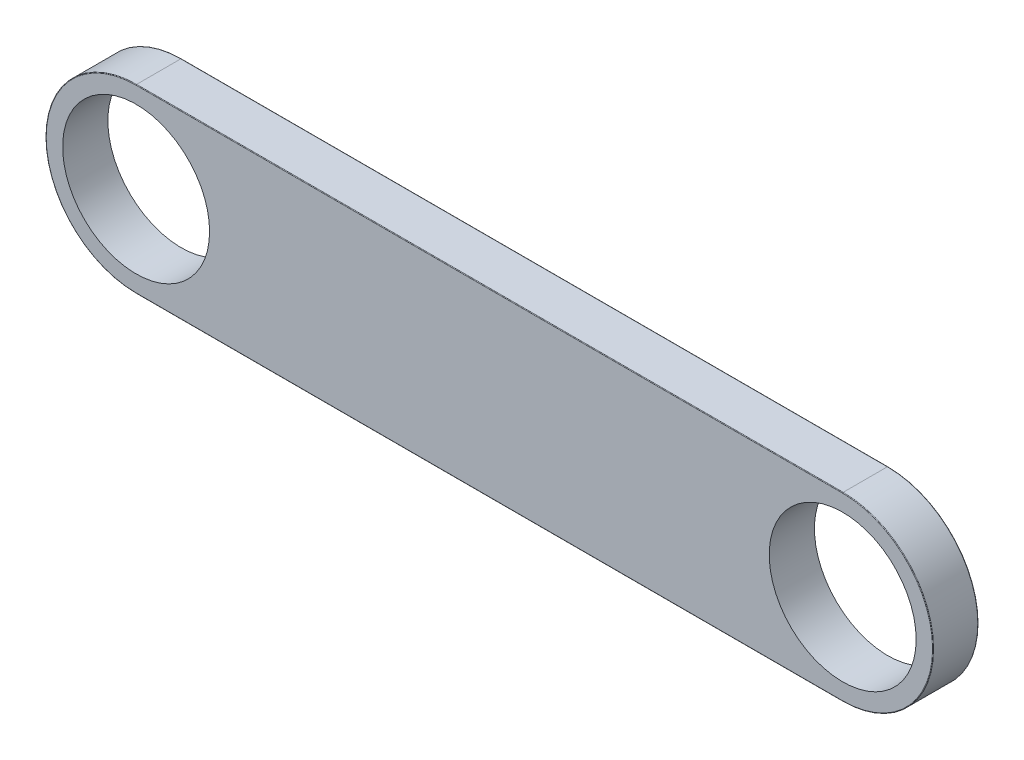
SolidWorks part; units mm, degrees
ref_plane "Front Plane" through (0, 0, 0) normal (0, 0, 1) x (1, 0, 0)
ref_plane "Top Plane" through (0, 0, 0) normal (0, 1, 0) x (1, 0, 0)
ref_plane "Right Plane" through (0, 0, 0) normal (1, 0, 0) x (0, 0, -1)
sketch "Sketch1" plane through (0, 0, 0) normal (0, 0, 1) x (1, 0, 0)
  line L0 (0, 0) -> (125, 0) construction
  line L1 (0, 16) -> (125, 16)
  line L2 (0, -16) -> (125, -16)
  arc A0 (0, 16) -> (0, -16) centre (0, 0) ccw
  arc A1 (125, -16) -> (125, 16) centre (125, 0) ccw
  circle A2 centre (0, 0) radius 13
  circle A3 centre (125, 0) radius 13
  point P3 (62.5, 0)
  dimension "D1" = 16
  dimension "D2" = 26
  dimension "D3" = 125
extrude "Boss-Extrude1" add sketch "Sketch1" along normal blind 8
fillet "Fillet1" radius 0.1 8 edges at (141, 0, 0) (62.5, -16, 0) (-16, 0, 0) (141, 0, 8) (62.5, -16, 8) (-16, 0, 8) (62.5, 16, 0) (62.5, 16, 8)
